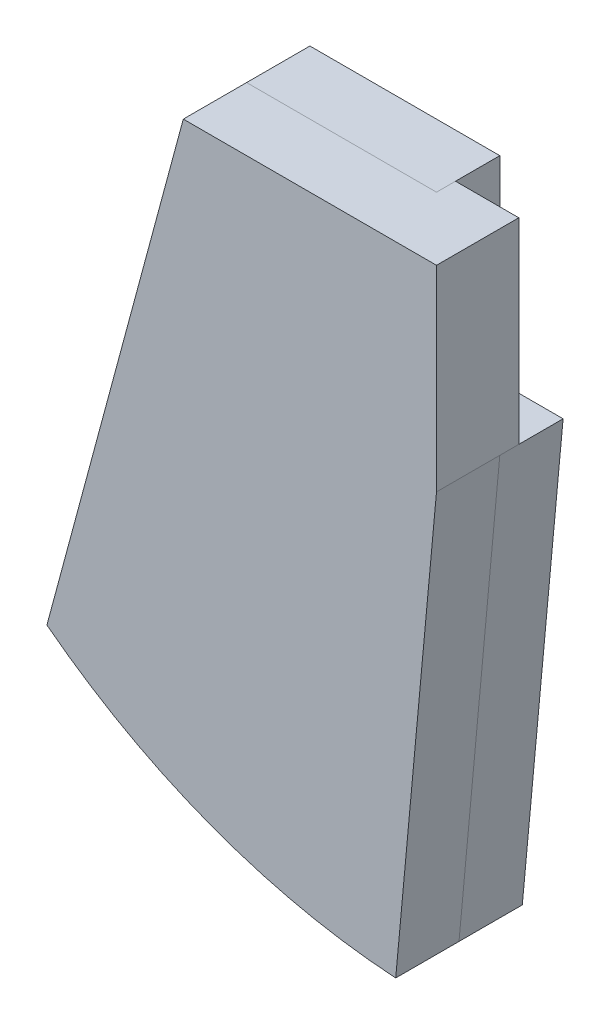
SolidWorks part; units mm, degrees
ref_plane "Front Plane" through (0, 0, 0) normal (0, 0, 1) x (1, 0, 0)
ref_plane "Top Plane" through (0, 0, 0) normal (0, 1, 0) x (1, 0, 0)
ref_plane "Right Plane" through (0, 0, 0) normal (1, 0, 0) x (0, 0, -1)
sketch "Sketch1" plane through (0, 0, 0) normal (0, 0, 1) x (1, 0, 0)
  line L0 (0, 0) -> (0, -21) construction
  line L1 (0, 0) -> (0, 5) construction
  line L2 (-5, -26) -> (5, -26)
  line L3 (-5, -26) -> (-5, 5)
  line L4 (-5, 5) -> (5, 5)
  line L5 (5, -26) -> (5, 5)
  line L6 (-5, -26) -> (5, 5) construction
  line L7 (-5, 5) -> (5, -26) construction
  line L8 (0, 0) -> (5, 0) construction
  point P3 (0, -10.5)
  dimension "D1" = 21
  dimension "D2" = 5
extrude "Boss-Extrude1" add sketch "Sketch1" along normal blind 3 contours L3 L4 L5 L2
sketch "Sketch2" plane through (0, 0, 0) normal (0, 0, -1) x (-1, 0, 0)
  circle A0 centre (0, 0) radius 1.5
  circle A1 centre (0, -21) radius 1.5
  dimension "D1" = 3
extrude "Cut-Extrude1" cut sketch "Sketch2" against normal blind 3
sketch "Sketch8" plane through (0, 0, 3) normal (0, 0, 1) x (1, 0, 0)
  line L0 (5, -26) -> (-1.4435, -95.7301)
  line L1 (-5, 5) -> (-35, 5)
  line L2 (-35, 5) -> (-56.5472, -75)
  line L7 (-5, -26) -> (5, -26)
  line L8 (5, -26) -> (5, 5)
  line L9 (5, 5) -> (-5, 5)
  line L10 (-5, 5) -> (-5, -26)
  line L12 (5, -26) -> (5, 5)
  line L13 (5, 5) -> (-5, 5)
  arc A0 (-56.5472, -75) -> (-1.4435, -95.7301) centre (5, 5) ccw
  dimension "D1" = 30
  dimension "D3" = 0
  dimension "D2" = 80
shell "Shell3" thickness 1 removed face at (-1.5, 0, 0)
extrude "Boss-Extrude2" add sketch "Sketch8" along normal blind 10
surface "Surface-Extrude1" parameters "D1"=10
